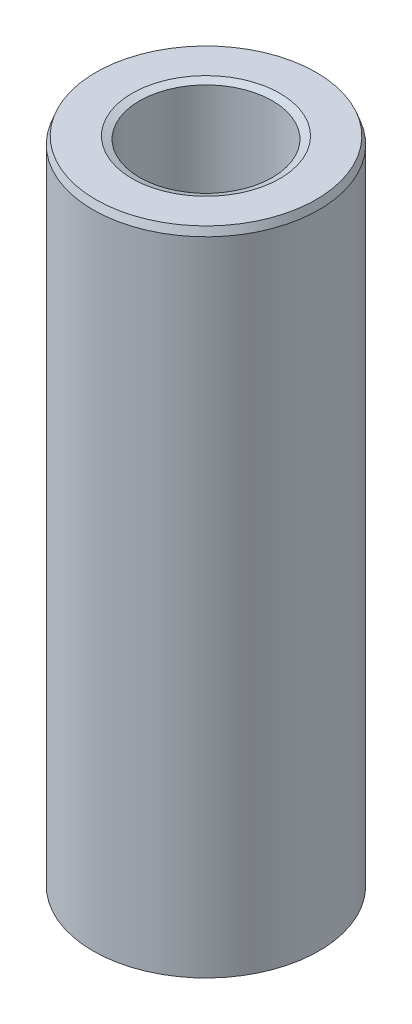
SolidWorks part; units mm, degrees
ref_plane "Front Plane" through (0, 0, 0) normal (0, 0, 1) x (1, 0, 0)
ref_plane "Top Plane" through (0, 0, 0) normal (0, 1, 0) x (1, 0, 0)
ref_plane "Right Plane" through (0, 0, 0) normal (1, 0, 0) x (0, 0, -1)
sketch "Sketch1" plane through (0, 0, 0) normal (0, 1, 0) x (1, 0, 0)
  circle A0 centre (0, 0) radius 55
  dimension "SLEEVE_OD" = 110
extrude "Boss-Extrude1" add sketch "Sketch1" along normal blind 317.5599
sketch "Sketch2" plane through (0, 0, 0) normal (0, 1, 0) x (1, 0, 0)
  circle A0 centre (0, 0) radius 32.3499
  dimension "BORE_D" = 64.6998
extrude "Cut-Extrude1" cut sketch "Sketch2" along normal through all
chamfer "Chamfer1" distance 3.6533 angle 20.075 4 edges at (0, 317.5599, 32.3499) (0, 0, 32.3499) (0, 0, 55) (0, 317.5599, 55) first distance on face at (0, 317.5599, 32.3499) first distance on face at (0, 0, 32.3499) first distance on face at (0, 317.5599, 55)
